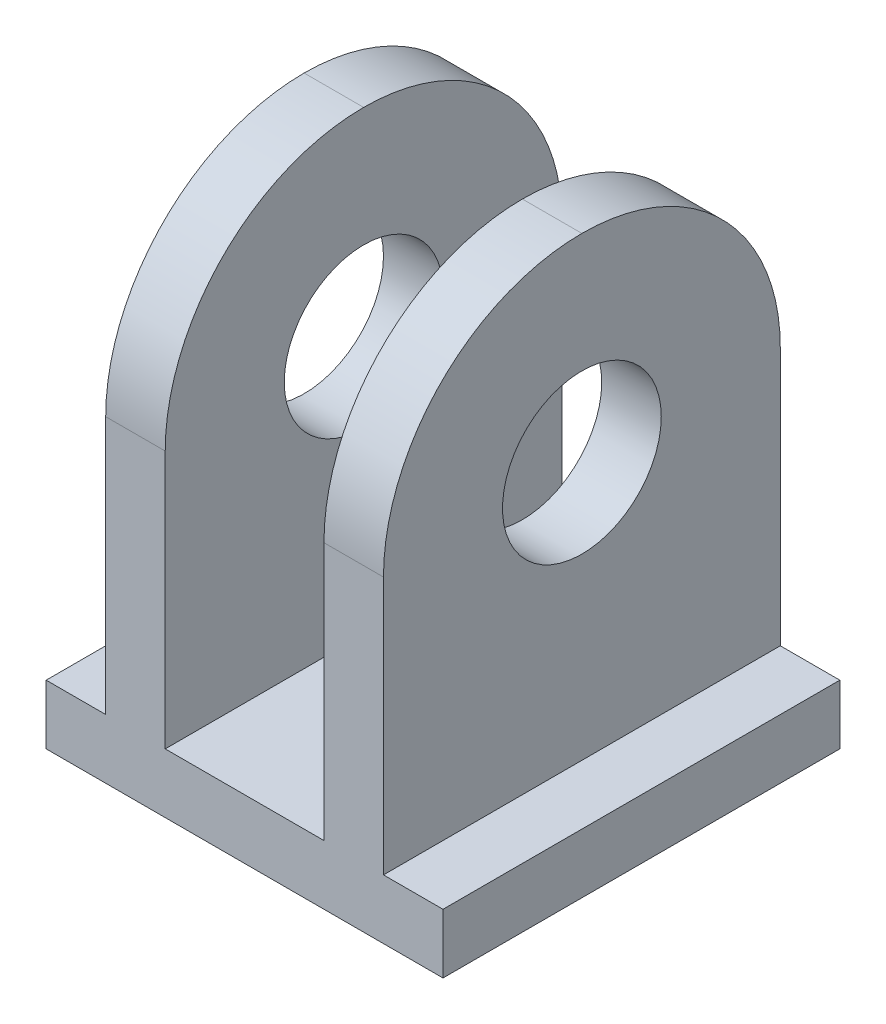
SolidWorks part; units mm, degrees
ref_plane "Alzado" through (0, 0, 0) normal (0, 0, 1) x (1, 0, 0)
ref_plane "Planta" through (0, 0, 0) normal (0, 1, 0) x (1, 0, 0)
ref_plane "Vista lateral" through (0, 0, 0) normal (1, 0, 0) x (0, 0, -1)
sketch "Croquis1" plane through (0, 0, 0) normal (0, 1, 0) x (1, 0, 0)
  line L1 (10, -10) -> (-10, -10)
  line L2 (10, -10) -> (10, 10)
  line L3 (10, 10) -> (-10, 10)
  line L4 (-10, -10) -> (-10, 10)
  line L5 (10, -10) -> (-10, 10) construction
  line L6 (10, 10) -> (-10, -10) construction
  point P0 (0, 0)
  dimension "D1" = 20
  dimension "D2" = 20
extrude "Saliente-Extruir1" add sketch "Croquis1" along normal blind 3
sketch "Croquis2" plane through (0, 3, 0) normal (0, 1, 0) x (1, 0, 0)
  line L0 (10, 10) -> (-10, 10) construction
  line L1 (-7, 10) -> (-4, 10)
  line L2 (-7, 10) -> (-7, -10)
  line L3 (-7, -10) -> (-4, -10)
  line L4 (-4, 10) -> (-4, -10)
  line L5 (-10, -10) -> (10, -10) construction
  line L6 (-10, 8.9544) -> (-7, 8.9544) construction
  line L7 (7, 10) -> (4, 10)
  line L8 (7, 10) -> (7, -10)
  line L9 (7, -10) -> (4, -10)
  line L10 (4, 10) -> (4, -10)
  line L11 (-10, 10) -> (-10, -10) construction
  line L12 (7, -11.3045) -> (10, -11.3045) construction
  line L13 (10, -10) -> (10, 10) construction
  dimension "D1" = 3
  dimension "D2" = 3
  dimension "D3" = 3
extrude "Saliente-Extruir2" add sketch "Croquis2" along normal blind 23
fillet "Redondeo1" radius 10 4 edges at (-5.5, 26, -10) (5.5, 26, -10) (5.5, 26, 10) (-5.5, 26, 10)
sketch "Croquis3" plane through (7, 0, 0) normal (1, 0, 0) x (0, 0, -1)
  circle A0 centre (0, 16) radius 4
  dimension "D1" = 8
extrude "Cortar-Extruir1" cut sketch "Croquis3" against normal through all
sketch "Croquis4" plane through (0, 3, 0) normal (0, 1, 0) x (1, 0, 0)
  circle A0 centre (0, 0) radius 3
  dimension "D1" = 6
extrude "Cortar-Extruir2" cut sketch "Croquis4" against normal through all
chamfer "Chaflán1" distance 1 angle 45 1 edges at (0, 3, 3)
